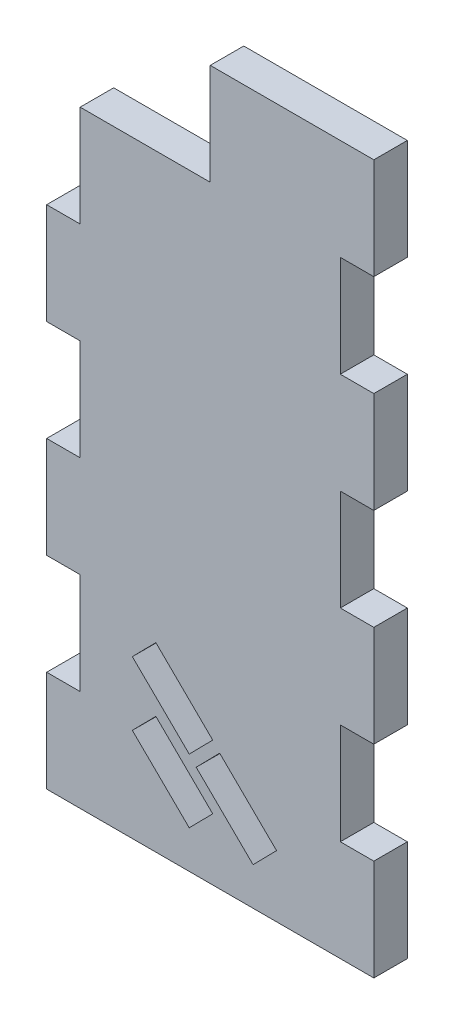
SolidWorks part; units mm, degrees
ref_plane "Front Plane" through (0, 0, 0) normal (0, 0, 1) x (1, 0, 0)
ref_plane "Top Plane" through (0, 0, 0) normal (0, 1, 0) x (1, 0, 0)
ref_plane "Right Plane" through (0, 0, 0) normal (1, 0, 0) x (0, 0, -1)
sketch "Sketch1" plane through (0, 0, 0) normal (0, 0, 1) x (1, 0, 0)
  line L1 (-39.922, 42.4532) -> (12.148, 42.4532)
  line L2 (-39.922, 42.4532) -> (-39.922, -70.3228)
  line L3 (-39.922, -70.3228) -> (12.148, -70.3228)
  line L4 (12.148, 42.4532) -> (12.148, -70.3228)
  dimension "D1" = 112.776
  dimension "D2" = 52.07
extrude "Boss-Extrude1" add sketch "Sketch1" along normal blind 5.334
sketch "Sketch2" plane through (0, 0, 5.334) normal (0, 0, 1) x (1, 0, 0)
  line L0 (-39.922, 42.4532) -> (-39.922, -70.3228) construction
  line L1 (-39.922, 26.3424) -> (-34.588, 26.3424)
  line L2 (-39.922, 26.3424) -> (-39.922, 10.2315)
  line L3 (-39.922, 10.2315) -> (-34.588, 10.2315)
  line L4 (-34.588, 26.3424) -> (-34.588, 10.2315)
  line L5 (-34.588, 26.3424) -> (-34.588, 42.4532) construction
  line L6 (-39.922, -5.8794) -> (-34.588, -5.8794)
  line L7 (-39.922, -5.8794) -> (-39.922, -21.9902)
  line L8 (-39.922, -21.9902) -> (-34.588, -21.9902)
  line L9 (-34.588, -5.8794) -> (-34.588, -21.9902)
  line L10 (-39.922, -38.1011) -> (-34.588, -38.1011)
  line L11 (-39.922, -38.1011) -> (-39.922, -54.2119)
  line L12 (-39.922, -54.2119) -> (-34.588, -54.2119)
  line L13 (-34.588, -38.1011) -> (-34.588, -54.2119)
  line L14 (12.148, 42.4532) -> (-39.922, 42.4532) construction
  line L15 (-34.588, 10.2315) -> (-34.588, -5.8794) construction
  line L16 (-34.588, -21.9902) -> (-34.588, -38.1011) construction
  line L17 (-34.588, -54.2119) -> (-34.588, -70.3228) construction
  line L18 (-39.922, -70.3228) -> (12.148, -70.3228) construction
  line L19 (-13.887, 42.4532) -> (-13.887, -70.3228) construction
  line L20 (6.814, -54.2119) -> (6.814, -70.3228) construction
  line L21 (6.814, -21.9902) -> (6.814, -38.1011) construction
  line L22 (6.814, 10.2315) -> (6.814, -5.8794) construction
  line L23 (6.814, 26.3424) -> (6.814, 42.4532) construction
  line L24 (6.814, -38.1011) -> (6.814, -54.2119)
  line L25 (12.148, -54.2119) -> (6.814, -54.2119)
  line L26 (12.148, -38.1011) -> (12.148, -54.2119)
  line L27 (12.148, -38.1011) -> (6.814, -38.1011)
  line L28 (6.814, -5.8794) -> (6.814, -21.9902)
  line L29 (12.148, -21.9902) -> (6.814, -21.9902)
  line L30 (12.148, -5.8794) -> (12.148, -21.9902)
  line L31 (12.148, -5.8794) -> (6.814, -5.8794)
  line L32 (6.814, 26.3424) -> (6.814, 10.2315)
  line L33 (12.148, 10.2315) -> (6.814, 10.2315)
  line L34 (12.148, 26.3424) -> (12.148, 10.2315)
  line L35 (12.148, 26.3424) -> (6.814, 26.3424)
  line L36 (-34.588, -54.2119) -> (-34.588, -70.3228) construction
  dimension "D1" = 5.334
extrude "Cut-Extrude1" cut sketch "Sketch2" against normal through all
sketch "Sketch3" plane through (0, 0, 5.334) normal (0, 0, 1) x (1, 0, 0)
  line L0 (6.814, -54.2119) -> (6.814, -70.3228) construction
  line L1 (-39.922, -70.3228) -> (12.148, -70.3228) construction
  line L2 (6.814, -70.3228) -> (-39.922, -24.3488) construction
  line L3 (-39.922, -21.9902) -> (-39.922, -38.1011) construction
  line L4 (-22.5448, -41.4427) -> (-13.491, -50.3488)
  line L5 (-22.5448, -41.4427) -> (-26.2854, -45.2453)
  line L6 (-13.491, -50.3488) -> (-17.2316, -54.1514)
  line L7 (-26.2854, -45.2453) -> (-17.2316, -54.1514)
  line L8 (-22.5448, -51.6027) -> (-13.491, -60.5088)
  line L9 (-22.5448, -51.6027) -> (-26.2854, -55.4053)
  line L10 (-13.491, -60.5088) -> (-17.2316, -64.3114)
  line L11 (-26.2854, -55.4053) -> (-17.2316, -64.3114)
  line L12 (-12.3848, -51.6027) -> (-3.331, -60.5088)
  line L13 (-12.3848, -51.6027) -> (-16.1254, -55.4053)
  line L14 (-16.1254, -55.4053) -> (-7.0716, -64.3114)
  line L15 (-3.331, -60.5088) -> (-7.0716, -64.3114)
  dimension "D1" = 5.334
  dimension "D2" = 12.7
  dimension "D3" = 2
extrude "Cut-Extrude2" cut sketch "Sketch3" against normal through all
sketch "Sketch4" plane through (0, 0, 5.334) normal (0, 0, 1) x (1, 0, 0)
  line L0 (-39.922, 26.3424) -> (12.148, 26.3424) construction
  line L1 (12.148, 26.3424) -> (6.814, 26.3424) construction
  line L2 (-13.887, 42.4532) -> (-13.887, 26.3424) construction
  line L3 (12.148, 42.4532) -> (-39.922, 42.4532) construction
  line L5 (-39.922, 42.4532) -> (-13.887, 42.4532)
  line L6 (-39.922, 42.4532) -> (-39.922, 26.3424)
  line L7 (-39.922, 26.3424) -> (-13.887, 26.3424)
  line L8 (-13.887, 42.4532) -> (-13.887, 26.3424)
extrude "Cut-Extrude3" cut sketch "Sketch4" against normal through all
equation "\"MDF\"= .21in"
equation "\"Foamcore\"= .13in"
equation "\"Gmaterial\"= \"MDF\""
equation "\"D2@Sketch1\"=\"MDF\"+1.63+\"MDF\""
equation "\"D1@Boss-Extrude1\"=\"MDF\""
equation "\"D1@Sketch2\"=\"MDF\""
equation "\"D1@Sketch3\"=\"MDF\""
equation "\"D2@Sketch3\"=.5"
